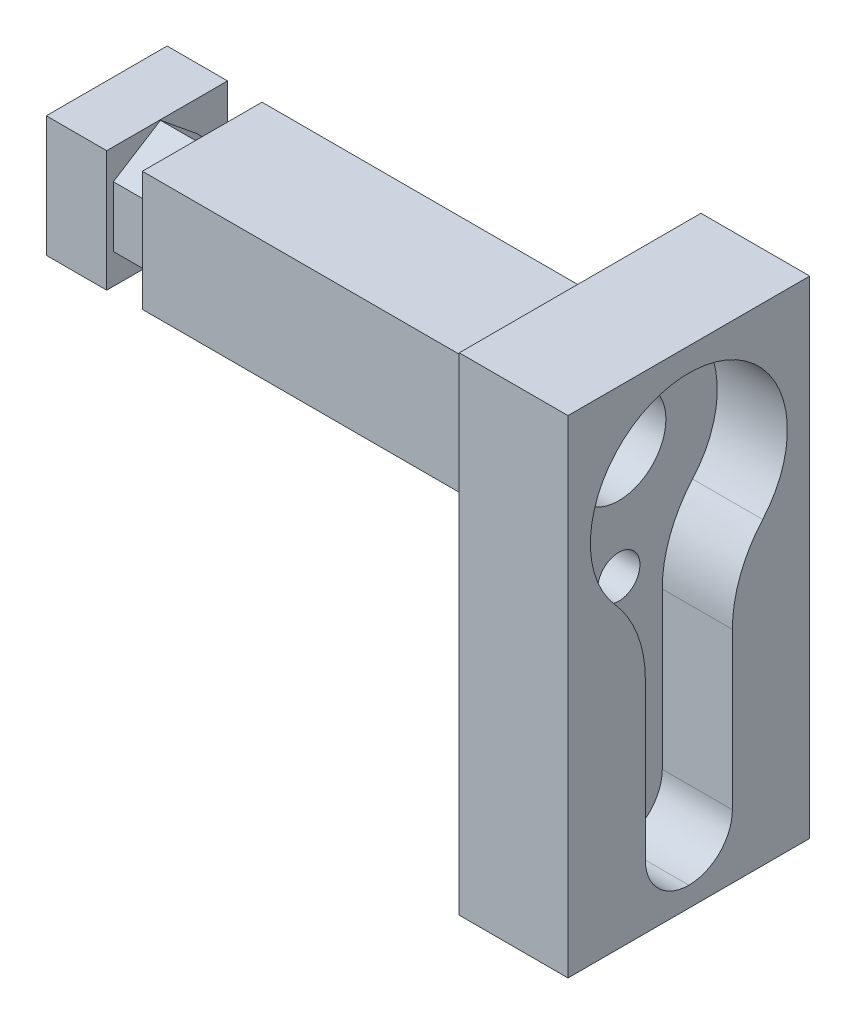
SolidWorks part; units mm, degrees
ref_plane "Front Plane" through (0, 0, 0) normal (0, 0, 1) x (1, 0, 0)
ref_plane "Top Plane" through (0, 0, 0) normal (0, 1, 0) x (1, 0, 0)
ref_plane "Right Plane" through (0, 0, 0) normal (1, 0, 0) x (0, 0, -1)
sketch "Sketch1" plane through (0, 0, 0) normal (1, 0, 0) x (0, 0, -1)
  line L1 (-10, 10) -> (10, 10)
  line L2 (-10, 10) -> (-10, -10)
  line L3 (-10, -10) -> (10, -10)
  line L4 (10, 10) -> (10, -10)
  line L5 (-10, 10) -> (10, -10) construction
  line L6 (-10, -10) -> (10, 10) construction
  point P0 (0, 0)
  dimension "D1" = 20
  dimension "D2" = 20
extrude "Boss-Extrude1" add sketch "Sketch1" along normal blind 20
sketch "Sketch2" plane through (20, 0, 0) normal (1, 0, 0) x (0, 0, -1)
  line L1 (-22.5, 35) -> (22.5, 35)
  line L2 (-22.5, 35) -> (-22.5, -35)
  line L3 (-22.5, -35) -> (22.5, -35)
  line L4 (22.5, 35) -> (22.5, -35)
  line L5 (-22.5, 35) -> (22.5, -35) construction
  line L6 (-22.5, -35) -> (22.5, 35) construction
  point P0 (0, 0)
  dimension "D1" = 45
  dimension "D2" = 70
extrude "Boss-Extrude2" add sketch "Sketch2" along normal blind 12
sketch "Sketch4" plane through (32, 0, 0) normal (1, 0, 0) x (0, 0, -1)
  line L0 (0, 7.65) -> (0, 8.1702) construction
  line L1 (7.65, 7.65) -> (-7.65, 7.65) construction
  line L17 (3.6, -26.55) -> (-3.6, -26.55) construction
  line L18 (-7.65, 7.65) -> (7.65, 7.65) construction
  line L22 (-7.65, 7.65) -> (-7.65, -27.55) construction
  line L23 (-7.65, -27.55) -> (7.65, -27.55) construction
  line L24 (7.65, 7.65) -> (7.65, -27.55) construction
  line L25 (-7.65, 7.65) -> (7.65, -27.55) construction
  line L26 (-7.65, -27.55) -> (7.65, 7.65) construction
  line L27 (3.6, -26.55) -> (3.6, -28.55) construction
  line L28 (3.6, -28.55) -> (-3.6, -28.55) construction
  line L29 (-3.6, -26.55) -> (-3.6, -28.55) construction
  line L30 (3.6, -26.55) -> (-3.6, -28.55) construction
  line L31 (3.6, -28.55) -> (-3.6, -26.55) construction
  line L34 (3.6, -28.55) -> (-3.6, -28.55)
  line L35 (-3.6, -28.55) -> (-3.6, -7.3118)
  line L36 (3.6, -28.55) -> (3.6, -7.3118)
  arc A1 (3.6, -6.75) -> (-3.6, -6.75) centre (0, 0) ccw construction
  arc A2 (3.6, -7.3118) -> (-3.6, -7.3118) centre (0, 0) ccw
  point P1 (0, -27.55)
  point P7 (0, -13.75)
  point P10 (0, 7.65)
  point P14 (0, -9.95)
  dimension "D1" = 15.3
  dimension "D5" = 2
  dimension "D2" = 15.3
  dimension "D3" = 35.2
  dimension "D4" = 7.2
extrude "Cut-Extrude1" cut sketch "Sketch4" against normal blind 5.8
fillet "Fillet1" radius 3.6 2 edges at (29.1, -28.55, 3.6) (29.1, -28.55, -3.6)
fillet "Fillet2" radius 10 2 edges at (29.1, -7.3118, 3.6) (29.1, -7.3118, -3.6)
sketch "Sketch5" plane through (0, 0, 0) normal (-1, 0, 0) x (0, 0, 1)
  circle A0 centre (0, 0) radius 3.9
  dimension "D1" = 7.8
extrude "Cut-Extrude2" cut sketch "Sketch5" against normal through all
sketch "Sketch6" plane through (26.2, 0, 0) normal (1, 0, 0) x (0, 0, -1)
  line L0 (0, -19.35) -> (0, 0) construction
  line L1 (0, -25.65) -> (0, -23.15) construction
  line L2 (0, -23.15) -> (0, -21.85) construction
  line L3 (0, -21.85) -> (0, -19.35) construction
  line L5 (0, 0) -> (1.164, 0) construction
  line L6 (0, 0) -> (0, -9.35) construction
  line L7 (0, -9.35) -> (1.164, -9.35) construction
  line L8 (1.164, 0) -> (1.164, -9.35) construction
  line L9 (0, 0) -> (1.164, -9.35) construction
  line L10 (0, -9.35) -> (1.164, 0) construction
  circle A0 centre (0, -20.6) radius 1.75
  circle A1 centre (0, -9.35) radius 1.75
  point P11 (0.582, -4.675)
  dimension "D5" = 3.5
  dimension "D6" = 9.35
  dimension "D7" = 3.5
  dimension "D1" = 19.35
  dimension "D2" = 2.5
  dimension "D3" = 1.3
  dimension "D4" = 2.5
extrude "Cut-Extrude3" cut sketch "Sketch6" against normal up to next
sketch "Sketch7" plane through (0, -35, 0) normal (0, -1, 0) x (1, 0, 0)
  line L1 (32, 22.5) -> (20, 22.5)
  line L2 (32, 22.5) -> (32, -22.5)
  line L3 (32, -22.5) -> (20, -22.5)
  line L4 (20, 22.5) -> (20, -22.5)
  line L5 (32, 22.5) -> (20, -22.5) construction
  line L6 (32, -22.5) -> (20, 22.5) construction
  point P5 (26, 0)
extrude "Cut-Extrude4" cut sketch "Sketch7" against normal blind 4.8
sketch "Sketch9" plane through (0, 35, 0) normal (0, 1, 0) x (1, 0, 0)
  line L1 (32, 22.5) -> (20, 22.5)
  line L2 (32, 22.5) -> (32, -22.5)
  line L3 (32, -22.5) -> (20, -22.5)
  line L4 (20, 22.5) -> (20, -22.5)
  line L5 (32, 22.5) -> (20, -22.5) construction
  line L6 (32, -22.5) -> (20, 22.5) construction
  point P4 (26, 0)
extrude "Cut-Extrude5" cut sketch "Sketch9" against normal blind 23.8
sketch "Sketch10" plane through (20, 0, 0) normal (-1, 0, 0) x (0, 0, 1)
  line L0 (-22.5, 11.2) -> (22.5, 11.2) construction
  line L1 (-10, 11.2) -> (-22.5, 11.2)
  line L2 (-10, 11.2) -> (-10, -30.2)
  line L3 (-10, -30.2) -> (-22.5, -30.2)
  line L4 (-22.5, 11.2) -> (-22.5, -30.2)
  line L5 (-10, 11.2) -> (-22.5, -30.2) construction
  line L6 (-10, -30.2) -> (-22.5, 11.2) construction
  line L7 (22.5, -30.2) -> (-22.5, -30.2) construction
  line L9 (10, 11.2) -> (22.5, 11.2)
  line L10 (10, 11.2) -> (10, -30.2)
  line L11 (10, -30.2) -> (22.5, -30.2)
  line L12 (22.5, 11.2) -> (22.5, -30.2)
  line L13 (10, 11.2) -> (22.5, -30.2) construction
  line L14 (10, -30.2) -> (22.5, 11.2) construction
  point P4 (-16.25, -9.5)
  point P13 (16.25, -9.5)
extrude "Cut-Extrude6" cut sketch "Sketch10" against normal blind 23.8
sketch "Sketch11" plane through (20, 0, 0) normal (-1, 0, 0) x (0, 0, 1)
  line L5 (-10, 11.2) -> (10, 11.2)
  line L6 (-10, 11.2) -> (-10, 10)
  line L7 (-10, 10) -> (10, 10)
  line L8 (10, 11.2) -> (10, 10)
  line L9 (-10, 11.2) -> (10, 10) construction
  line L10 (-10, 10) -> (10, 11.2) construction
  point P4 (0, 10.6)
extrude "Cut-Extrude7" cut sketch "Sketch11" against normal blind 23.8
sketch "Sketch12" plane through (0, 0, 0) normal (-1, 0, 0) x (0, 0, 1)
  line L1 (10, 10) -> (-10, 10)
  line L2 (10, 10) -> (10, -10)
  line L3 (10, -10) -> (-10, -10)
  line L4 (-10, 10) -> (-10, -10)
  line L5 (10, 10) -> (-10, -10) construction
  line L6 (10, -10) -> (-10, 10) construction
  circle A0 centre (0, 0) radius 3.9
  point P4 (0, 0)
extrude "Boss-Extrude3" add sketch "Sketch12" along normal blind 20
sketch "Sketch13" plane through (-20, 0, 0) normal (-1, 0, 0) x (0, 0, 1)
  line L8 (10.1, -10.1) -> (10.1, 10.1)
  line L9 (10.1, 10.1) -> (-10.1, 10.1)
  line L10 (-10.1, 10.1) -> (-10.1, -10.1)
  line L11 (-10.1, -10.1) -> (10.1, -10.1)
  line L12 (10.1, -10.1) -> (10.1, 10.1)
  line L13 (10.1, 10.1) -> (-10.1, 10.1)
  line L14 (-10.1, 10.1) -> (-10.1, -10.1)
  line L15 (-10.1, -10.1) -> (10.1, -10.1)
  circle A0 centre (0, 0) radius 3.9
  dimension "D1" = 0.1
extrude "Boss-Extrude4" add sketch "Sketch13" against normal up to surface (40 mm away) up to face at (20, -20.6, -1.75)
sketch "Sketch14" plane through (0, 10, 0) normal (0, 1, 0) x (1, 0, 0)
  line L1 (32, 10) -> (20, 10)
  line L2 (32, 10) -> (32, -10)
  line L3 (32, -10) -> (20, -10)
  line L4 (20, 10) -> (20, -10)
  line L5 (32, 10) -> (20, -10) construction
  line L6 (32, -10) -> (20, 10) construction
  point P4 (26, 0)
extrude "Boss-Extrude5" add sketch "Sketch14" along normal blind 0.1
sketch "Sketch17" plane through (-20, 0, 0) normal (-1, 0, 0) x (0, 0, 1)
  circle A0 centre (0, 0) radius 4.8309
extrude "Boss-Extrude8" add sketch "Sketch17" against normal blind 39
sketch "Sketch18" plane through (-20, 0, 0) normal (-1, 0, 0) x (0, 0, 1)
  line L5 (10.1, 10.1) -> (-15.5388, 10.1)
  line L6 (10.1, 10.1) -> (10.1, -36.522)
  line L7 (10.1, -36.522) -> (-15.5388, -36.522)
  line L8 (-15.5388, 10.1) -> (-15.5388, -36.522)
  line L9 (10.1, 10.1) -> (-15.5388, -36.522) construction
  line L10 (10.1, -36.522) -> (-15.5388, 10.1) construction
  point P4 (-2.7194, -13.211)
extrude "Cut-Extrude8" cut sketch "Sketch18" against normal blind 43
sketch "Sketch19" plane through (23, 0, 0) normal (-1, 0, 0) x (0, 0, 1)
  line L1 (4.95, 4.95) -> (-4.95, 4.95)
  line L2 (4.95, 4.95) -> (4.95, -4.95)
  line L3 (4.95, -4.95) -> (-4.95, -4.95)
  line L4 (-4.95, 4.95) -> (-4.95, -4.95)
  line L5 (4.95, 4.95) -> (-4.95, -4.95) construction
  line L6 (4.95, -4.95) -> (-4.95, 4.95) construction
  point P0 (0, 0)
  dimension "D1" = 9.9
  dimension "D2" = 9.9
extrude "Boss-Extrude9" add sketch "Sketch19" along normal blind 31.27
sketch "Sketch20" plane through (-8.27, 0, 0) normal (-1, 0, 0) x (0, 0, 1)
  line L0 (-4.95, 0) -> (-4.95, 2.5) construction
  line L1 (-4.95, 4.95) -> (-4.95, -4.95) construction
  line L2 (-4.95, 0) -> (-4.95, -2.5) construction
  line L3 (-4.95, 2.5) -> (4.95, 2.5) construction
  line L4 (4.95, -4.95) -> (4.95, 4.95) construction
  line L5 (-4.95, -2.5) -> (4.95, -2.5) construction
  line L6 (-4.95, 4.95) -> (0.55, 4.95) construction
  line L7 (4.95, 4.95) -> (-4.95, 4.95) construction
  line L8 (-4.95, -4.95) -> (0.55, -4.95) construction
  line L9 (-4.95, -4.95) -> (4.95, -4.95) construction
  line L10 (0.55, 4.95) -> (-2.45, 2.5)
  line L11 (-4.95, 2.5) -> (-2.45, 2.5) construction
  line L12 (0.55, 4.95) -> (4.45, 2.5)
  line L13 (4.95, 2.5) -> (4.45, 2.5) construction
  line L14 (4.95, 2.5) -> (4.95, -2.5) construction
  line L15 (4.95, -2.5) -> (4.45, -2.5) construction
  line L16 (4.45, 2.5) -> (4.45, -2.5) construction
  line L17 (4.95, 2.5) -> (4.45, -2.5) construction
  line L18 (4.95, -2.5) -> (4.45, 2.5) construction
  line L19 (4.45, 2.5) -> (4.45, -2.5)
  line L20 (4.45, -2.5) -> (0.55, -4.95)
  line L21 (-4.95, 2.5) -> (-4.95, -2.5) construction
  line L22 (-4.95, -2.5) -> (-2.45, -2.5) construction
  line L23 (-2.45, 2.5) -> (-2.45, -2.5) construction
  line L24 (-4.95, 2.5) -> (-2.45, -2.5) construction
  line L25 (-4.95, -2.5) -> (-2.45, 2.5) construction
  line L26 (-2.45, 2.5) -> (-2.45, -2.5)
  line L27 (-2.45, -2.5) -> (0.55, -4.95)
  point P21 (4.7, 0)
  point P24 (-3.7, 0)
  dimension "D1" = 2.5
  dimension "D2" = 2.5
  dimension "D3" = 5.5
  dimension "D4" = 5.5
  dimension "D5" = 0.5
  dimension "D6" = 2.5
extrude "Boss-Extrude10" add sketch "Sketch20" along normal blind 2.9
sketch "Sketch21" plane through (-11.17, 0, 0) normal (-1, 0, 0) x (0, 0, 1)
  line L1 (5, 5) -> (-5, 5)
  line L2 (5, 5) -> (5, -5)
  line L3 (5, -5) -> (-5, -5)
  line L4 (-5, 5) -> (-5, -5)
  line L5 (5, 5) -> (-5, -5) construction
  line L6 (5, -5) -> (-5, 5) construction
  point P0 (0, 0)
  dimension "D1" = 10
  dimension "D2" = 10
extrude "Boss-Extrude11" add sketch "Sketch21" along normal blind 5
fillet "Fillet4" radius 4 3 edges at (23, 0, 4.95) (23, 4.95, 0) (23, 0, -4.95)
fillet "Fillet5" radius 1 1 edges at (23, -4.95, 0)
